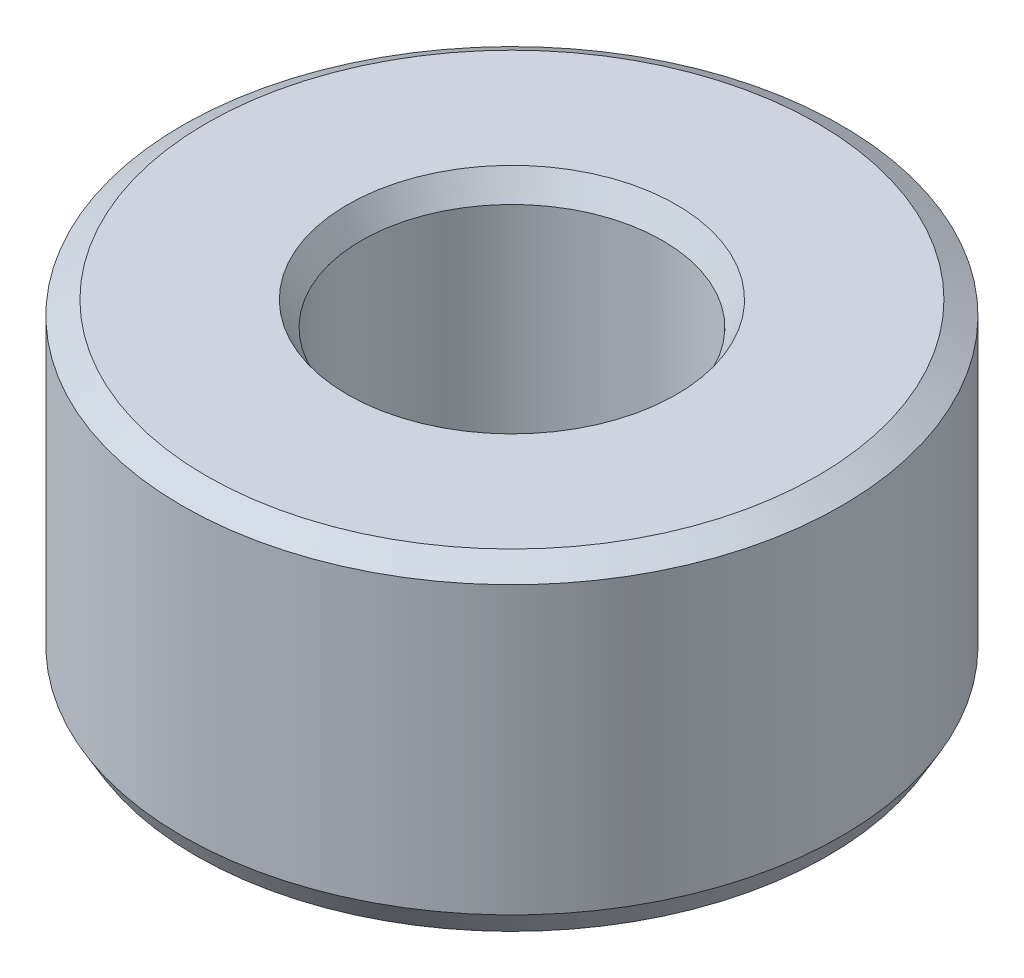
SolidWorks part; units mm, degrees
ref_plane "Front Plane" through (0, 0, 0) normal (0, 0, 1) x (1, 0, 0)
ref_plane "Top Plane" through (0, 0, 0) normal (0, 1, 0) x (1, 0, 0)
ref_plane "Right Plane" through (0, 0, 0) normal (1, 0, 0) x (0, 0, -1)
sketch "Sketch1" plane through (0, 0, 0) normal (0, 1, 0) x (1, 0, 0)
  circle A0 centre (0, 0) radius 10
  dimension "SLEEVE_OD" = 20
extrude "Boss-Extrude1" add sketch "Sketch1" along normal blind 9.8293
sketch "Sketch2" plane through (0, 0, 0) normal (0, 1, 0) x (1, 0, 0)
  circle A0 centre (0, 0) radius 4.5694
  dimension "BORE_D" = 9.1388
extrude "Cut-Extrude1" cut sketch "Sketch2" along normal through all
chamfer "Chamfer1" distance 0.4217 angle 60 4 edges at (0, 9.8293, 4.5694) (0, 0, 4.5694) (0, 0, 10) (0, 9.8293, 10) first distance on face at (0, 9.8293, 4.5694) first distance on face at (0, 0, 4.5694) first distance on face at (0, 9.8293, 10)
